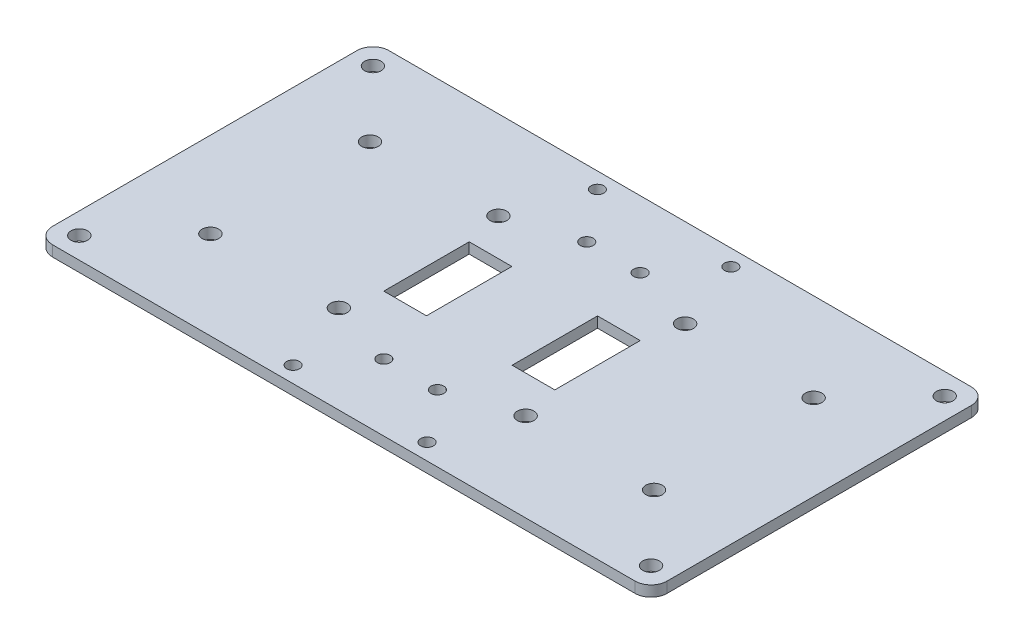
SolidWorks part; units mm, degrees
ref_plane "Plano frontal" through (0, 0, 0) normal (0, 0, 1) x (1, 0, 0)
ref_plane "Plano superior" through (0, 0, 0) normal (0, 1, 0) x (1, 0, 0)
ref_plane "Plano direito" through (0, 0, 0) normal (1, 0, 0) x (0, 0, -1)
sketch "Esboço1" plane through (0, 0, 0) normal (0, 1, 0) x (1, 0, 0)
  line L7 (-57.5484, 31.5) -> (57.5484, 31.5)
  line L8 (57.5484, 31.5) -> (57.5484, -31.5)
  line L9 (57.5484, -31.5) -> (-57.5484, -31.5)
  line L10 (-57.5484, -31.5) -> (-57.5484, 31.5)
  line L11 (0, 31.5) -> (0, -31.5) construction
  line L12 (-57.5484, 0) -> (57.5484, 0) construction
  dimension "D1" = 63
  dimension "D2" = 115.0968
extrude "Ressalto-extrusão1" add sketch "Esboço1" along normal blind 2
sketch "Esboço2" plane through (0, 2, 0) normal (0, 1, 0) x (1, 0, 0)
  line L0 (-57.5484, 0) -> (57.5484, 0) construction
  line L1 (-57.5484, 31.5) -> (-57.5484, -31.5) construction
  line L2 (-57.5484, -31.5) -> (57.5484, -31.5) construction
  line L5 (57.5484, -31.5) -> (57.5484, 31.5) construction
  line L6 (0, -31.5) -> (0, 31.5) construction
  line L7 (57.5484, 31.5) -> (-57.5484, 31.5) construction
  circle A8 centre (-41.5484, -14.945) radius 1.55
  circle A10 centre (-17.4884, -14.94) radius 1.55
  circle A11 centre (17.4884, -14.94) radius 1.55
  circle A12 centre (41.5484, -14.945) radius 1.55
  circle A13 centre (41.5484, 14.945) radius 1.55
  circle A14 centre (17.4884, 14.94) radius 1.55
  circle A15 centre (-17.4884, 14.94) radius 1.55
  circle A16 centre (-41.5484, 14.945) radius 1.55
  dimension "D1" = 16.555
  dimension "D3" = 3.1
  dimension "D4" = 16.56
  dimension "D2" = 24.06
  dimension "D5" = 16
extrude "Corte-extrusão1" cut sketch "Esboço2" against normal through all
sketch "Esboço5" plane through (0, 2, 0) normal (0, 1, 0) x (1, 0, 0)
  line L2 (57.5484, 31.5) -> (-57.5484, 31.5) construction
  line L3 (57.5484, -31.5) -> (57.5484, 31.5) construction
  line L4 (57.5484, 0) -> (-57.5484, 0) construction
  line L5 (-57.5484, 31.5) -> (-57.5484, -31.5) construction
  line L6 (0, 31.5) -> (0, -31.5) construction
  line L7 (-57.5484, -31.5) -> (57.5484, -31.5) construction
  line L8 (53.5484, -13.175) -> (53.5484, -27.5) construction
  line L9 (-53.5484, -13.175) -> (-53.5484, -27.5) construction
  line L10 (-53.5484, 21.175) -> (-53.5484, 35.5) construction
  circle A0 centre (53.5484, 27.5) radius 1.55
  circle A1 centre (53.5484, -27.5) radius 1.55
  circle A2 centre (-53.5484, -27.5) radius 1.55
  circle A3 centre (-53.5484, 27.5) radius 1.55
  dimension "D2" = 3.1
  dimension "D1" = 4
  dimension "D3" = 4
extrude "Corte-extrusão3" cut sketch "Esboço5" against normal through all
fillet "Filete1" radius 3 4 edges at (57.5484, 1, -31.5) (57.5484, 1, 31.5) (-57.5484, 1, 31.5) (-57.5484, 1, -31.5)
sketch "Esboço8" plane through (0, 2, 0) normal (0, 1, 0) x (1, 0, 0)
  line L0 (-57.5484, 28.5) -> (-57.5484, -28.5) construction
  line L1 (54.5484, 31.5) -> (-54.5484, 31.5) construction
  line L2 (0, 0) -> (0, 31.5) construction
  line L3 (57.5484, 0) -> (-57.5484, 0) construction
  line L5 (57.5484, -28.5) -> (57.5484, 28.5) construction
  circle A15 centre (-12.5, -28.5) radius 1.2
  circle A16 centre (-5, -19) radius 1.2
  circle A17 centre (5.0094, -18.9811) radius 1.2
  circle A18 centre (12.5451, -28.4528) radius 1.2
  circle A19 centre (12.5451, 28.4528) radius 1.2
  circle A20 centre (5.0094, 18.9811) radius 1.2
  circle A21 centre (-5, 19) radius 1.2
  circle A22 centre (-12.5, 28.5) radius 1.2
extrude "Corte-extrusão4" cut sketch "Esboço8" against normal through all
sketch "Esboço9" plane through (0, 0, 0) normal (0, -1, 0) x (1, 0, 0)
  line L0 (-8.0184, 8) -> (-16.0184, 8)
  line L1 (-16.0184, 8) -> (-16.0184, -8)
  line L2 (-16.0184, -8) -> (-8.0184, -8)
  line L3 (-8.0184, -8) -> (-8.0184, 8)
  line L4 (0, 31.5) -> (0, -31.5) construction
  line L5 (-54.5484, 31.5) -> (54.5484, 31.5) construction
  line L6 (54.5484, -31.5) -> (-54.5484, -31.5) construction
  line L7 (8.0184, -8) -> (8.0184, 8)
  line L8 (16.0184, -8) -> (8.0184, -8)
  line L9 (16.0184, 8) -> (16.0184, -8)
  line L10 (8.0184, 8) -> (16.0184, 8)
extrude "Corte-extrusão5" cut sketch "Esboço9" against normal through all
